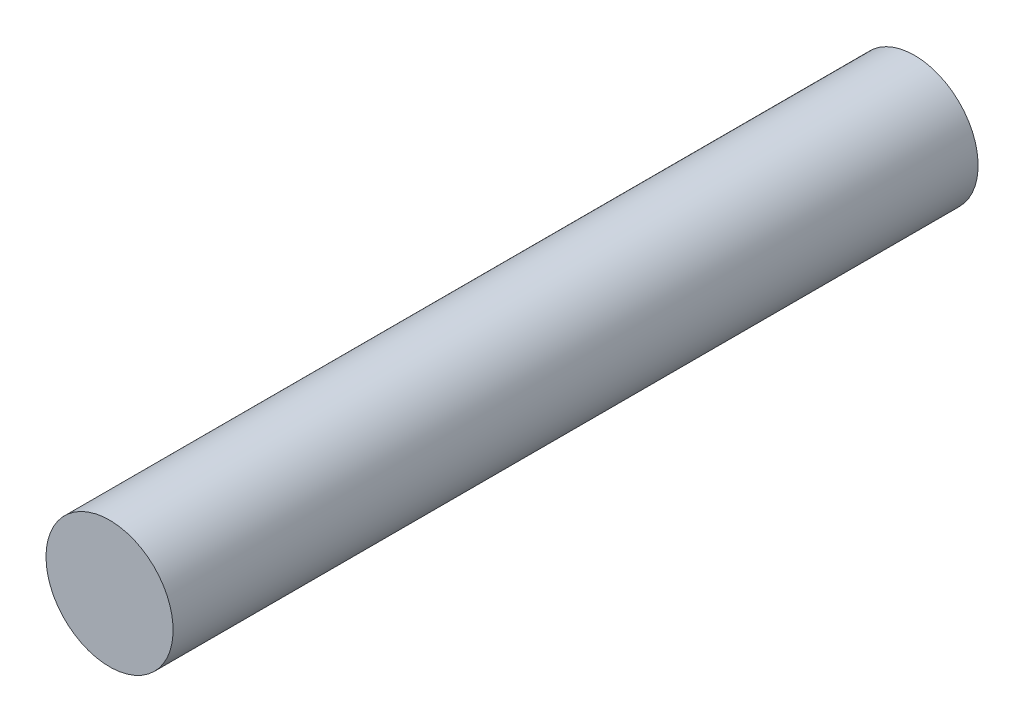
SolidWorks part; units mm, degrees
ref_plane "Front Plane" through (0, 0, 0) normal (0, 0, 1) x (1, 0, 0)
ref_plane "Top Plane" through (0, 0, 0) normal (0, 1, 0) x (1, 0, 0)
ref_plane "Right Plane" through (0, 0, 0) normal (1, 0, 0) x (0, 0, -1)
sketch "Sketch1" plane through (0, 0, 0) normal (0, 0, 1) x (1, 0, 0)
  circle A0 centre (0, 0) radius 9.525
  point P2 (0, 0)
  dimension "D1" = 19.05
extrude "Boss-Extrude2" add sketch "Sketch1" along normal blind 120.65
